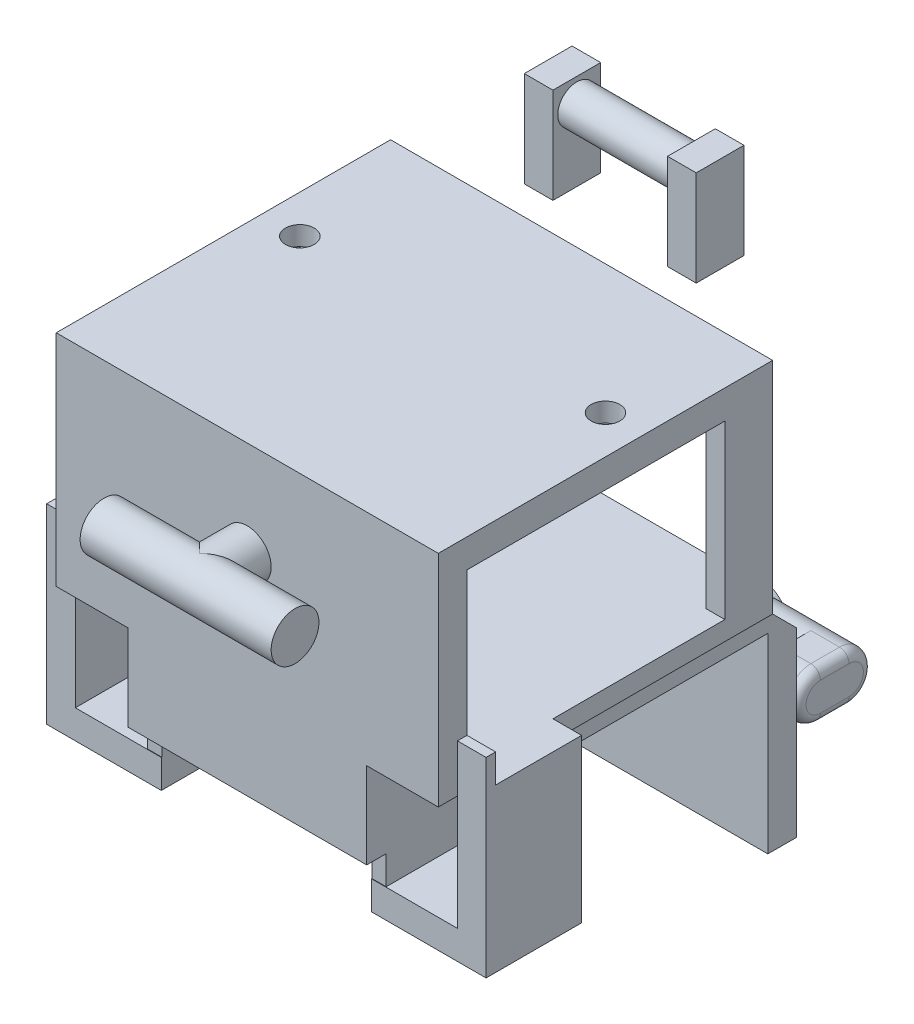
SolidWorks part; units mm, degrees
ref_plane "正面" through (0, 0, 0) normal (0, 0, 1) x (1, 0, 0)
ref_plane "平面" through (0, 0, 0) normal (0, 1, 0) x (1, 0, 0)
ref_plane "右側面" through (0, 0, 0) normal (1, 0, 0) x (0, 0, -1)
sketch "ｽｹｯﾁ1" plane through (0, 0, 0) normal (0, 1, 0) x (1, 0, 0)
  line L1 (0, 0) -> (25, 0)
  line L2 (0, 0) -> (0, 42)
  line L3 (0, 42) -> (25, 42)
  line L4 (25, 0) -> (25, 42)
  dimension "D1" = 25
  dimension "D2" = 42
extrude "ﾎﾞｽ - 押し出し1" add sketch "ｽｹｯﾁ1" along normal blind 9
sketch "ｽｹｯﾁ2" plane through (0, 0, -42) normal (0, 0, -1) x (-1, 0, 0)
  line L1 (-25, 9) -> (0, 9)
  line L2 (-25, 9) -> (-25, -20)
  line L3 (-25, -20) -> (0, -20)
  line L4 (0, 9) -> (0, -20)
  dimension "D1" = 29
extrude "ﾎﾞｽ - 押し出し2" add sketch "ｽｹｯﾁ2" along normal blind 3
sketch "ｽｹｯﾁ3" plane through (0, 9, 0) normal (0, 1, 0) x (1, 0, 0)
  line L0 (0, 45) -> (25, 45) construction
  line L1 (-7.5, 0) -> (32.5, 0)
  line L2 (-7.5, 0) -> (-7.5, 35)
  line L3 (-7.5, 35) -> (32.5, 35)
  line L4 (32.5, 0) -> (32.5, 35)
  line L6 (0, 0) -> (25, 0) construction
  line L7 (0, 45) -> (0, 0) construction
  dimension "D1" = 40
  dimension "D2" = 7.5
  dimension "D4" = 10
extrude "ﾎﾞｽ - 押し出し3" add sketch "ｽｹｯﾁ3" along normal blind 23
sketch "ｽｹｯﾁ4" plane through (0, 0, -45) normal (0, 0, -1) x (-1, 0, 0)
  line L0 (-32.5, 32) -> (7.5, 32) construction
  line L1 (5.5, 30) -> (-30.5, 30)
  line L2 (5.5, 30) -> (5.5, 11)
  line L3 (5.5, 11) -> (-30.5, 11)
  line L4 (-30.5, 30) -> (-30.5, 11)
  line L5 (7.5, 32) -> (7.5, 9) construction
  line L6 (-32.5, 32) -> (-32.5, 9) construction
  line L7 (0, 9) -> (7.5, 9) construction
  dimension "D1" = 2
  dimension "D2" = 2
  dimension "D3" = 2
  dimension "D4" = 2
extrude "ｶｯﾄ - 押し出し1" cut sketch "ｽｹｯﾁ4" against normal blind 43
sketch "ｽｹｯﾁ6" plane through (32.5, 0, 0) normal (1, 0, 0) x (0, 0, -1)
  line L0 (42, 0) -> (42, -20) construction
  line L1 (2, -6) -> (12, -6)
  line L2 (2, -6) -> (2, 14)
  line L3 (2, 14) -> (12, 14)
  line L4 (12, -6) -> (12, 14)
  line L5 (0, 9) -> (35, 9) construction
  dimension "D1" = 30
  dimension "D2" = 20
  dimension "D3" = 10
  dimension "D4" = 15
extrude "ﾎﾞｽ - 押し出し4" add sketch "ｽｹｯﾁ6" along normal blind 3
sketch "ｽｹｯﾁ7" plane through (0, -6, 0) normal (0, -1, 0) x (1, 0, 0)
  line L0 (35.5, -2) -> (32.5, -2) construction
  line L1 (32.5, -12) -> (23.5, -12)
  line L2 (32.5, -12) -> (32.5, -2)
  line L3 (32.5, -2) -> (23.5, -2)
  line L4 (23.5, -12) -> (23.5, -2)
  dimension "D1" = 9
extrude "ﾎﾞｽ - 押し出し5" add sketch "ｽｹｯﾁ7" against normal blind 3
ref_plane "平面1" through (12.5, 0, 0) normal (1, 0, 0) x (0, 0, -1)
mirror "ﾐﾗｰ1" about plane through (12.5, 0, 0) normal (1, 0, 0) of "ﾎﾞｽ - 押し出し4", "ﾎﾞｽ - 押し出し5"
sketch "ｽｹｯﾁ8" plane through (0, 32, 0) normal (0, 1, 0) x (1, 0, 0)
  line L0 (12.5, -15.95) -> (12.5, 15.95) construction
  line L1 (3.5, 43) -> (6.5, 43)
  line L2 (3.5, 43) -> (3.5, 38)
  line L3 (3.5, 38) -> (6.5, 38)
  line L4 (6.5, 43) -> (6.5, 38)
  line L5 (21.5, 38) -> (18.5, 38)
  line L6 (18.5, 43) -> (18.5, 38)
  line L7 (21.5, 43) -> (18.5, 43)
  line L8 (21.5, 43) -> (21.5, 38)
  line L10 (32.5, 35) -> (-7.5, 35) construction
  dimension "D1" = 5
  dimension "D2" = 3
  dimension "D3" = 12
  dimension "D4" = 8
extrude "ﾎﾞｽ - 押し出し6" add sketch "ｽｹｯﾁ8" along normal blind 10
sketch "ｽｹｯﾁ9" plane through (6.5, 0, 0) normal (1, 0, 0) x (0, 0, -1)
  line L0 (38, 42) -> (38, 32) construction
  line L1 (38, 42) -> (43, 42) construction
  circle A0 centre (40.5, 39.5) radius 2
  dimension "D1" = 4
  dimension "D2" = 2.5
  dimension "D3" = 2.5
extrude "ﾎﾞｽ - 押し出し7" add sketch "ｽｹｯﾁ9" along normal up to next (12 mm away)
sketch "ｽｹｯﾁ10" plane through (-7.5, 0, 0) normal (-1, 0, 0) x (0, 0, 1)
  line L0 (-2, 9) -> (0, 9) construction
  line L1 (0, 32) -> (0, 9) construction
  circle A0 centre (-7, 19) radius 1.5
  dimension "D1" = 3
  dimension "D2" = 10
  dimension "D3" = 7
extrude "ｶｯﾄ - 押し出し2" cut sketch "ｽｹｯﾁ10" against normal through all
sketch "ｽｹｯﾁ11" plane through (0, 0, -45) normal (0, 0, -1) x (-1, 0, 0)
  line L1 (-25, -20) -> (0, -20) construction
  line L2 (-12.5, 15.95) -> (-12.5, -15.95) construction
  circle A0 centre (-12.5, -10) radius 2.5
  dimension "D1" = 5
  dimension "D2" = 10
extrude "ﾎﾞｽ - 押し出し8" add sketch "ｽｹｯﾁ11" along normal blind 9
sketch "ｽｹｯﾁ12" plane through (12.5, 0, 0) normal (1, 0, 0) x (0, 0, -1)
  line L0 (45, -12.5) -> (45, -7.5) construction
  line L2 (45, -12.5) -> (54, -12.5) construction
  circle A0 centre (52, -10) radius 2.5
  dimension "D1" = 5
  dimension "D2" = 7
  dimension "D3" = 2.5
extrude "ﾎﾞｽ - 押し出し9" add sketch "ｽｹｯﾁ12" along normal blind 7
sketch "ｽｹｯﾁ13" plane through (19.5, 0, 0) normal (1, 0, 0) x (0, 0, -1)
  line L0 (52, -10) -> (49, -10) construction
  line L1 (52, -12.5) -> (49, -12.5)
  line L2 (52, -7.5) -> (49, -7.5)
  arc A0 (52, -12.5) -> (52, -7.5) centre (52, -10) ccw
  arc A1 (49, -7.5) -> (49, -12.5) centre (49, -10) ccw
  circle A2 centre (52, -10) radius 2.5 construction
  point P2 (50.5, -10)
  dimension "D1" = 2.5
  dimension "D2" = 3
extrude "ﾎﾞｽ - 押し出し10" add sketch "ｽｹｯﾁ13" along normal blind 4
fillet "ﾌｨﾚｯﾄ1" radius 1 4 edges at (23.5, -12.5, -50.5) (23.5, -10, -46.5) (23.5, -7.5, -50.5) (23.5, -10, -54.5)
mirror "ﾐﾗｰ2" about plane through (12.5, 0, 0) normal (1, 0, 0) of "ﾌｨﾚｯﾄ1", "ﾎﾞｽ - 押し出し10", "ﾎﾞｽ - 押し出し9"
sketch "ｽｹｯﾁ19" plane through (30.5, 0, 0) normal (-1, 0, 0) x (0, 0, 1)
  line L0 (-2, 11) -> (-35, 11) construction
  line L1 (-30, 11) -> (-3, 11)
  line L2 (-30, 11) -> (-30, 29)
  line L3 (-30, 29) -> (-3, 29)
  line L4 (-3, 11) -> (-3, 29)
  line L6 (-35, 32) -> (-35, 9) construction
  dimension "D1" = 27
  dimension "D2" = 5
  dimension "D3" = 18
extrude "ｶｯﾄ - 押し出し5" cut sketch "ｽｹｯﾁ19" against normal through all both and the other way through all
sketch "ｽｹｯﾁ20" plane through (0, 32, 0) normal (0, 1, 0) x (1, 0, 0)
  line L0 (-7.5, 35) -> (-7.5, 0) construction
  line L1 (32.5, 0) -> (32.5, 35) construction
  line L2 (3.5, 38) -> (6.5, 38) construction
  line L3 (18.5, 38) -> (21.5, 38) construction
  circle A0 centre (-3.5, 21.5) radius 1.5
  circle A1 centre (28.5, 21.5) radius 1.5
  dimension "D1" = 3
  dimension "D2" = 3
  dimension "D3" = 4
  dimension "D4" = 4
  dimension "D5" = 16.5
  dimension "D6" = 16.5
extrude "ｶｯﾄ - 押し出し6" cut sketch "ｽｹｯﾁ20" against normal blind 10 and the other way through all
sketch "ｽｹｯﾁ21" plane through (0, 30, 0) normal (0, -1, 0) x (1, 0, 0)
  line L1 (-5.5, -2) -> (-5.5, -35) construction
  line L2 (22.5, -35) -> (19.5, -35)
  line L3 (22.5, -35) -> (22.5, -30)
  line L4 (22.5, -30) -> (19.5, -30)
  line L5 (19.5, -35) -> (19.5, -30)
  line L6 (5.5, -35) -> (2.5, -35)
  line L7 (5.5, -35) -> (5.5, -30)
  line L8 (5.5, -30) -> (2.5, -30)
  line L9 (2.5, -35) -> (2.5, -30)
  line L10 (32.5, -35) -> (-7.5, -35) construction
  dimension "D1" = 3
  dimension "D2" = 5
  dimension "D3" = 3
  dimension "D4" = 5
  dimension "D6" = 8
extrude "ﾎﾞｽ - 押し出し11" add sketch "ｽｹｯﾁ21" along normal blind 10
sketch "ｽｹｯﾁ22" plane through (19.5, 0, 0) normal (-1, 0, 0) x (0, 0, 1)
  line L0 (-30, 20) -> (-35, 20) construction
  line L1 (-30, 20) -> (-30, 30) construction
  circle A0 centre (-32.5, 22.5) radius 2.5
  dimension "D1" = 5
  dimension "D2" = 2.5
  dimension "D3" = 2.5
extrude "ﾎﾞｽ - 押し出し12" add sketch "ｽｹｯﾁ22" along normal up to next
sketch "ｽｹｯﾁ23" plane through (1.5, 0, 0) normal (1, 0, 0) x (0, 0, -1)
  line L0 (42, 0) -> (0, 0) construction
  line L1 (12, -3) -> (2.0458, -3)
  line L2 (12, -3) -> (12, 0)
  line L3 (12, 0) -> (2.0458, 0)
  line L4 (2.0458, -3) -> (2.0458, 0)
extrude "ﾎﾞｽ - 押し出し13" add sketch "ｽｹｯﾁ23" against normal blind 1.5
mirror "ﾐﾗｰ3" about plane through (12.5, 0, 0) normal (1, 0, 0) of "ﾎﾞｽ - 押し出し13"
sketch "ｽｹｯﾁ24" plane through (32.5, 0, 0) normal (1, 0, 0) x (0, 0, -1)
  line L0 (15, 32) -> (0, 32)
  line L1 (0, 32) -> (35, 32) construction
  line L2 (0, 32) -> (0, 17)
  line L3 (0, 32) -> (0, 9) construction
  line L4 (0, 17) -> (15, 32)
  dimension "D1" = 15
  dimension "D2" = 15
sketch "ｽｹｯﾁ25" plane through (25, 0, 0) normal (1, 0, 0) x (0, 0, -1)
  line L0 (35, 9) -> (45, -1)
  line L1 (45, 9) -> (45, -20) construction
  line L2 (45, -1) -> (45, 9)
  line L3 (45, 9) -> (35, 9)
  dimension "D1" = 10
extrude "ｶｯﾄ - 押し出し8" cut sketch "ｽｹｯﾁ25" against normal through all
sketch "ｽｹｯﾁ26" plane through (0, 0, 0) normal (0, 0, 1) x (1, 0, 0)
  line L0 (-7.5, 32) -> (32.5, 32) construction
  line L1 (-7.5, 32) -> (-7.5, 9) construction
  circle A0 centre (12.5, 22) radius 2.5
  point P4 (0, 0)
  point P6 (-4.9221, 22.876)
  dimension "D1" = 5
  dimension "D2" = 10
  dimension "D3" = 20
extrude "ﾎﾞｽ - 押し出し14" add sketch "ｽｹｯﾁ26" along normal blind 5
sketch "ｽｹｯﾁ27" plane through (12.5, 0, 0) normal (1, 0, 0) x (0, 0, -1)
  line L1 (35, 32) -> (0, 32) construction
  line L2 (0, 32) -> (0, 9) construction
  circle A0 centre (-5, 22) radius 2.5
  point P4 (0, 0)
  point P6 (-6.5259, 23.0134)
  point P8 (0, 0)
  dimension "D1" = 5
  dimension "D2" = 10
  dimension "D3" = 5
extrude "ﾎﾞｽ - 押し出し15" add sketch "ｽｹｯﾁ27" along normal blind 10 and the other way blind 10
